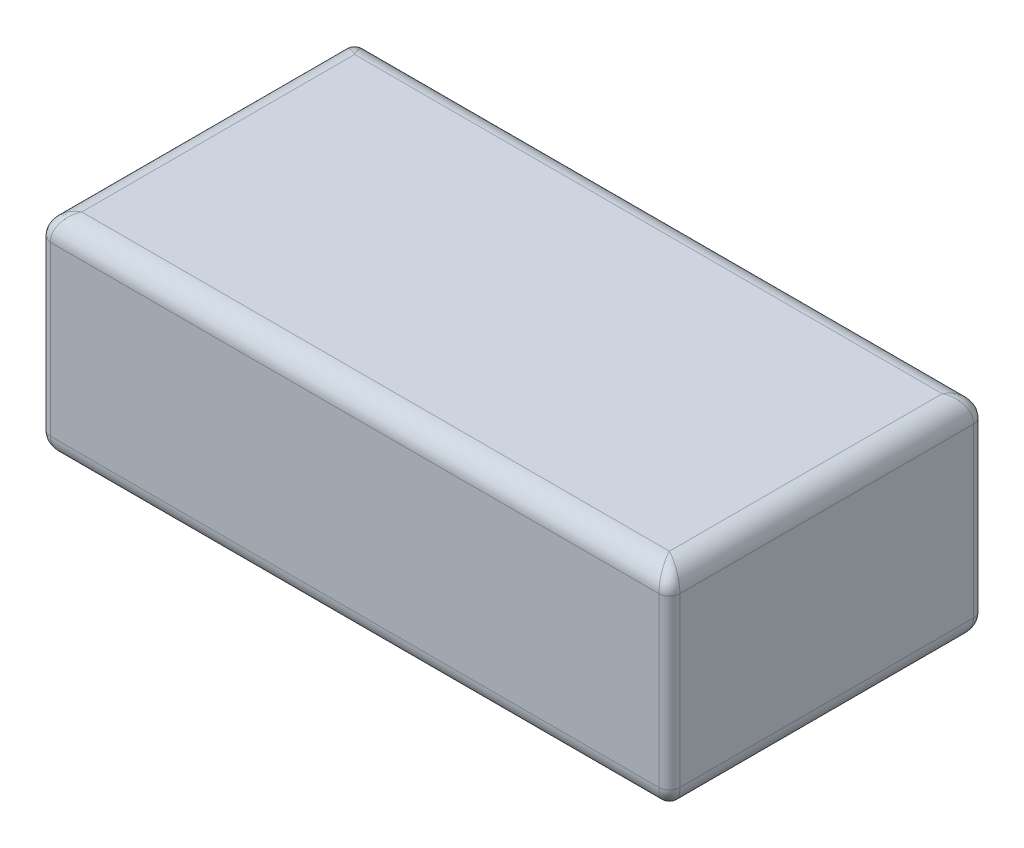
SolidWorks part; units mm, degrees
ref_plane "Front Plane" through (0, 0, 0) normal (0, 0, 1) x (1, 0, 0)
ref_plane "Top Plane" through (0, 0, 0) normal (0, 1, 0) x (1, 0, 0)
ref_plane "Right Plane" through (0, 0, 0) normal (1, 0, 0) x (0, 0, -1)
sketch "Sketch1" plane through (0, 0, 0) normal (0, 1, 0) x (1, 0, 0)
  line L5 (30, -15) -> (-30, -15)
  line L6 (30, -15) -> (30, 15)
  line L7 (30, 15) -> (-30, 15)
  line L8 (-30, -15) -> (-30, 15)
  line L9 (30, -15) -> (-30, 15) construction
  line L10 (30, 15) -> (-30, -15) construction
  point P0 (0, 0)
  dimension "D1" = 60
  dimension "D2" = 30
extrude "Boss-Extrude1" add sketch "Sketch1" along normal mid plane 20
fillet "Fillet1" radius 1 4 edges at (30, 0, -15) (30, 0, 15) (-30, 0, -15) (-30, 0, 15)
fillet "Fillet2" radius 2 16 edges at (-29.7071, -10, 14.7071) (-30, -10, 0) (-29.7071, -10, -14.7071) (0, -10, -15) (29.7071, -10, -14.7071) (30, -10, 0) (29.7071, -10, 14.7071) (-29.7071, 10, 14.7071) (-30, 10, 0) (-29.7071, 10, -14.7071) (0, 10, -15) (29.7071, 10, -14.7071) (30, 10, 0) (29.7071, 10, 14.7071) (0, -10, 15) (0, 10, 15)
